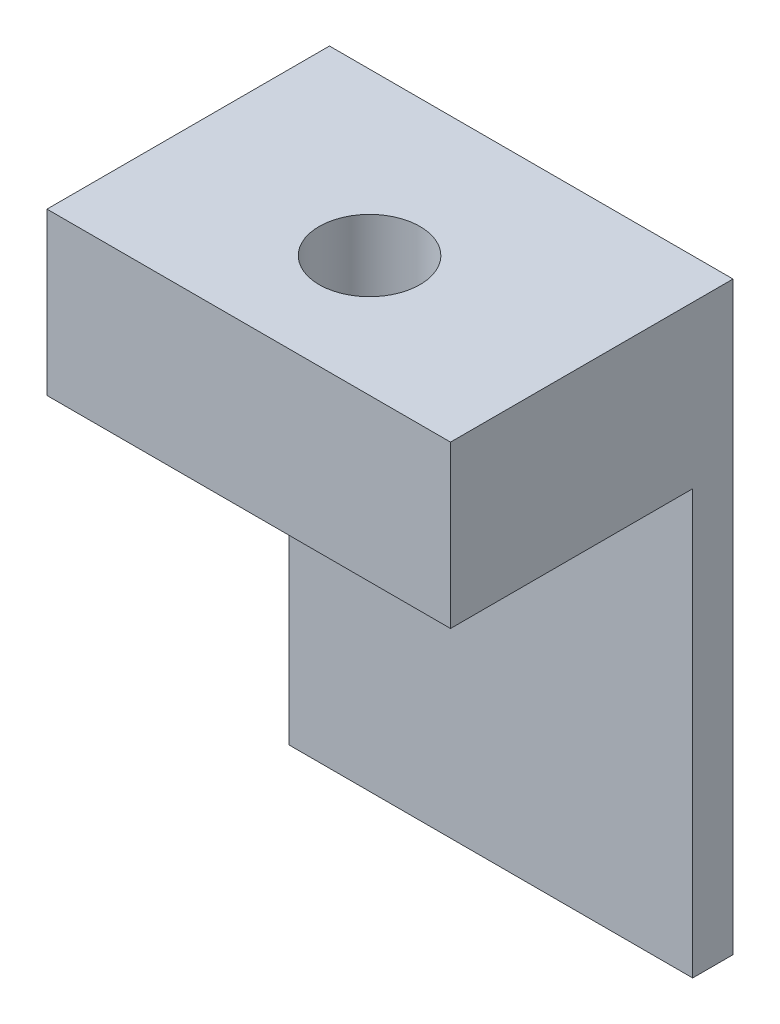
SolidWorks part; units mm, degrees
ref_plane "Front Plane" through (0, 0, 0) normal (0, 0, 1) x (1, 0, 0)
ref_plane "Top Plane" through (0, 0, 0) normal (0, 1, 0) x (1, 0, 0)
ref_plane "Right Plane" through (0, 0, 0) normal (1, 0, 0) x (0, 0, -1)
sketch "Sketch1" plane through (0, 0, 0) normal (1, 0, 0) x (0, 0, -1)
  line L1 (0.5, 7.25) -> (-0.5, 7.25)
  line L2 (0.5, 7.25) -> (0.5, -7.25)
  line L3 (0.5, -7.25) -> (-0.5, -7.25)
  line L4 (-0.5, 3.25) -> (-0.5, -7.25)
  line L5 (0.5, 7.25) -> (-0.5, -7.25) construction
  line L6 (0.5, -7.25) -> (-0.5, 7.25) construction
  line L7 (-0.5, 7.25) -> (-6.5, 7.25)
  line L9 (-0.5, 3.25) -> (-6.5, 3.25)
  line L10 (-6.5, 7.25) -> (-6.5, 3.25)
  point P0 (0, 0)
  dimension "D1" = 14.5
  dimension "D2" = 1
  dimension "D3" = 4
  dimension "D4" = 6
extrude "Boss-Extrude1" add sketch "Sketch1" along normal blind 10
sketch "Sketch2" plane through (0, 7.25, 0) normal (0, 1, 0) x (1, 0, 0)
  line L0 (4.9892, -6.1998) -> (5, 0.5) construction
  line L1 (10, 0.5) -> (0, 0.5) construction
  line L2 (10, -6.5) -> (0, -6.5) construction
  circle A0 centre (4.9935, -3.5) radius 1.25
  dimension "D1" = 2.5
  dimension "D2" = 3
extrude "Cut-Extrude1" cut sketch "Sketch2" against normal up to surface (4 mm away) up to face at (5, 3.25, 3.5)
